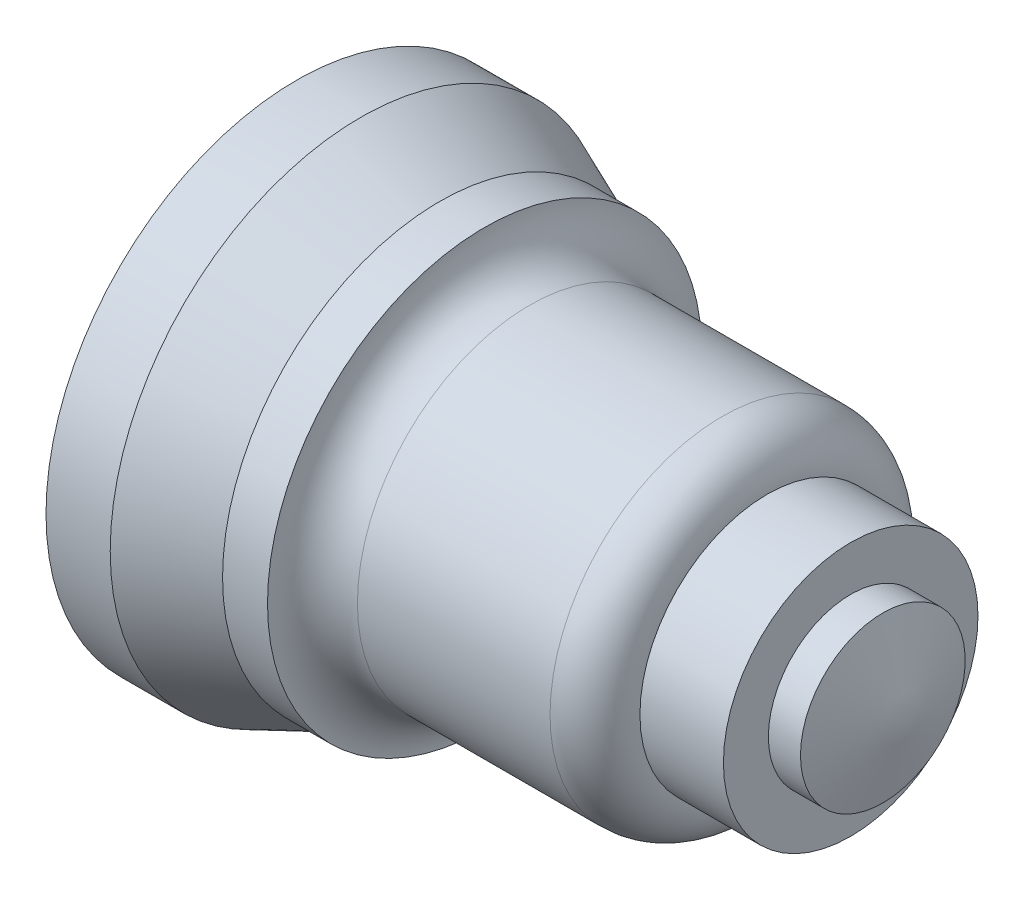
SolidWorks part; units mm, degrees
ref_plane "Front Plane" through (0, 0, 0) normal (0, 0, 1) x (1, 0, 0)
ref_plane "Top Plane" through (0, 0, 0) normal (0, 1, 0) x (1, 0, 0)
ref_plane "Right Plane" through (0, 0, 0) normal (1, 0, 0) x (0, 0, -1)
sketch "Sketch1" plane through (0, 0, 0) normal (0, 0, 1) x (1, 0, 0)
  line L0 (0, 0) -> (120.65, 0)
  line L23 (0, 0) -> (0, 49.53)
  line L30 (0, 49.53) -> (12.7, 49.53)
  line L32 (46.1245, 34.066) -> (84.2245, 34.066)
  line L33 (93.1145, 25.176) -> (109.6245, 25.176)
  line L34 (109.6245, 25.176) -> (109.6245, 16.286)
  line L35 (109.6245, 16.286) -> (115.9745, 16.286)
  line L36 (115.9745, 16.286) -> (120.65, 0)
  line L37 (37.2345, 42.956) -> (28.3445, 42.956)
  line L38 (12.7, 49.53) -> (28.3445, 42.956)
  arc A1 (37.2345, 42.956) -> (46.1245, 34.066) centre (46.1245, 42.956) ccw
  arc A4 (93.1145, 25.176) -> (84.2245, 34.066) centre (84.2245, 25.176) ccw
  dimension "D4" = 49.53
  dimension "D1" = 120.65
revolve "Revolve5" add sketch "Sketch1" angle 360 about L0
